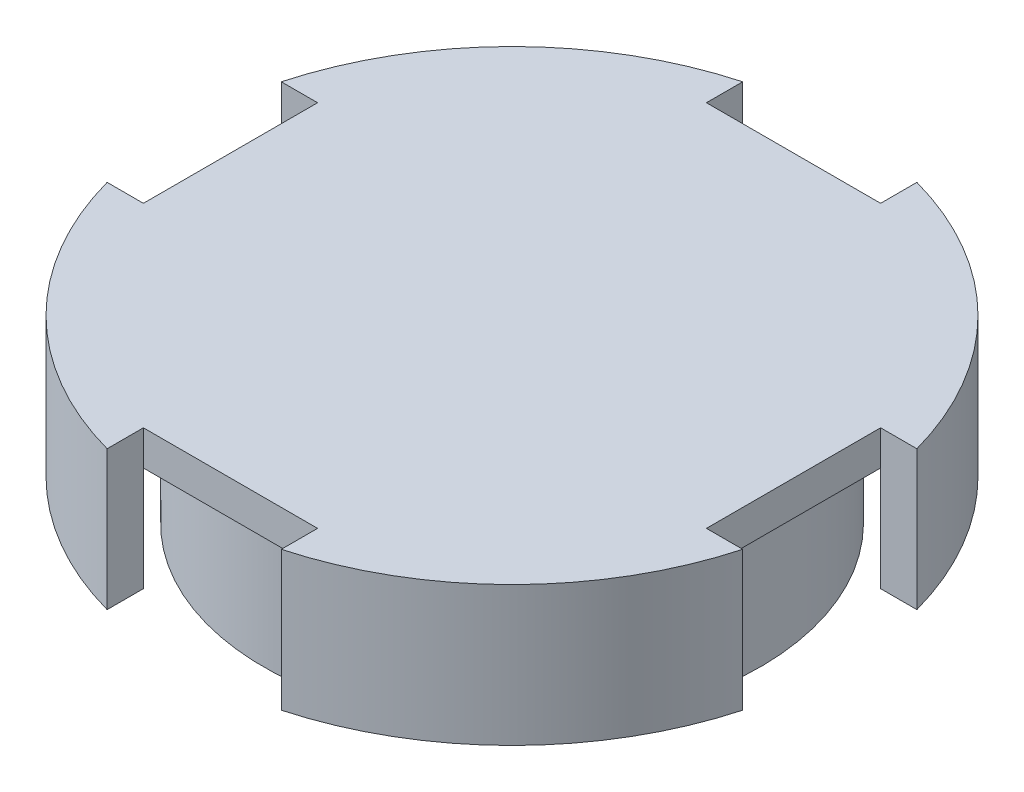
SolidWorks part; units mm, degrees
note: The reader was unsure of these and kept them because the rebuilt part matched: shared geometry of "Sketch1<3>", "Sketch2<3>", "Sketch2<4>".
ref_plane "Front Plane" through (0, 0, 0) normal (0, 0, 1) x (1, 0, 0)
ref_plane "Top Plane" through (0, 0, 0) normal (0, 1, 0) x (1, 0, 0)
ref_plane "Right Plane" through (0, 0, 0) normal (1, 0, 0) x (0, 0, -1)
sketch "Sketch1" plane through (0, 0, 0) normal (0, 1, 0) x (1, 0, 0)
  line L1 (-2.05, 16.3016) -> (2.05, 16.3016)
  line L2 (-2.05, 16.3016) -> (-2.05, 21.3016)
  line L3 (-2.05, 21.3016) -> (2.05, 21.3016)
  line L4 (2.05, 16.3016) -> (2.05, 21.3016)
  circle A0 centre (0, 0) radius 20.5
  circle A1 centre (0, 0) radius 23.5
  circle A2 centre (0, 0) radius 25
  circle A3 centre (0, 0) radius 21.4
  circle A4 centre (0, 0) radius 25.5
  circle A5 centre (8.6, 0) radius 1.55
  circle A6 centre (-8.6, 0) radius 1.55
  circle A7 centre (0, 0) radius 18.4
  point P16 (2.9158, 16.3388)
  point P17 (0, 16.3016)
  point P18 (0, 0)
  point P19 (0, 0)
  point P20 (0, 0)
  dimension "D1" = 41
  dimension "D3" = 50
  dimension "D4" = 51
  dimension "D5" = 42.8
  dimension "D6" = 3.1
  dimension "D2" = 3
  dimension "D7" = 8.6
  dimension "D8" = 8.6
  dimension "D9" = 3
  dimension "D10" = 5
  dimension "D11" = 4.1
extrude "Boss-Extrude1" add sketch "Sketch1" along normal blind 11.5 contours A0 A6 A5 | A3 A0 | A0 A7
extrude "Boss-Extrude2" add sketch "Sketch1<3>" along normal blind 11.5 and the other way blind 5 contours A6 | A5
sketch "Sketch1<3>" plane through (0, 0, 0) normal (0, 1, 0) x (1, 0, 0) same geometry as "Sketch1"
sketch "Sketch2" plane through (0, 0, 0) normal (0, 1, 0) x (1, 0, 0)
  line L0 (-7.5, 27.3659) -> (-7.5, 24.2413)
  line L1 (-7.5, 24.2413) -> (7.5, 24.2413)
  line L2 (7.5, 24.2413) -> (7.5, 27.3659)
  line L3 (24.2413, -7.5) -> (27.3659, -7.5)
  line L4 (24.2413, 7.5) -> (24.2413, -7.5)
  line L5 (27.3659, 7.5) -> (24.2413, 7.5)
  line L6 (-7.5, -24.2413) -> (-7.5, -27.3659)
  line L7 (7.5, -24.2413) -> (-7.5, -24.2413)
  line L8 (7.5, -27.3659) -> (7.5, -24.2413)
  line L9 (-24.2413, 7.5) -> (-27.3659, 7.5)
  line L10 (-24.2413, -7.5) -> (-24.2413, 7.5)
  line L11 (-27.3659, -7.5) -> (-24.2413, -7.5)
  circle A0 centre (0, 0) radius 21.4
  circle A1 centre (0, 0) radius 18.4
  circle A2 centre (0, 0) radius 25.375
  circle A3 centre (0, 0) radius 28.375
  point P8 (0, 0)
  point P11 (0, 0)
  point P25 (0, 0)
  dimension "D2" = 3
  dimension "D1" = 42.8
  dimension "D3" = 50.75
  dimension "D4" = 56.75
  dimension "D5" = 15
  dimension "D6" = 4
extrude "Boss-Extrude3" add sketch "Sketch2" along normal blind 4 from surface at 11.5 contours A0 A1 | A1 starting at face at (0, 11.5, -8.1262)
extrude "Boss-Extrude4" add sketch "Sketch2<3>" against normal blind 3 from surface at 15.5 contours A2 A0
sketch "Sketch2<3>" plane through (0, 0, 0) normal (0, 1, 0) x (1, 0, 0) same geometry as "Sketch2"
extrude "Boss-Extrude5" add sketch "Sketch2<4>" against normal blind 12 from surface at 15.5 contours A3 A2 | L11 A3 L6 A2 | L0 A3 L9 A2 | L5 A3 L2 A2
sketch "Sketch2<4>" plane through (0, 0, 0) normal (0, 1, 0) x (1, 0, 0) same geometry as "Sketch2"
equation "\"D8@Sketch1\"=\"D7@Sketch1\""
equation "\"D4@Sketch2\"=\"D3@Sketch2\"+6"
